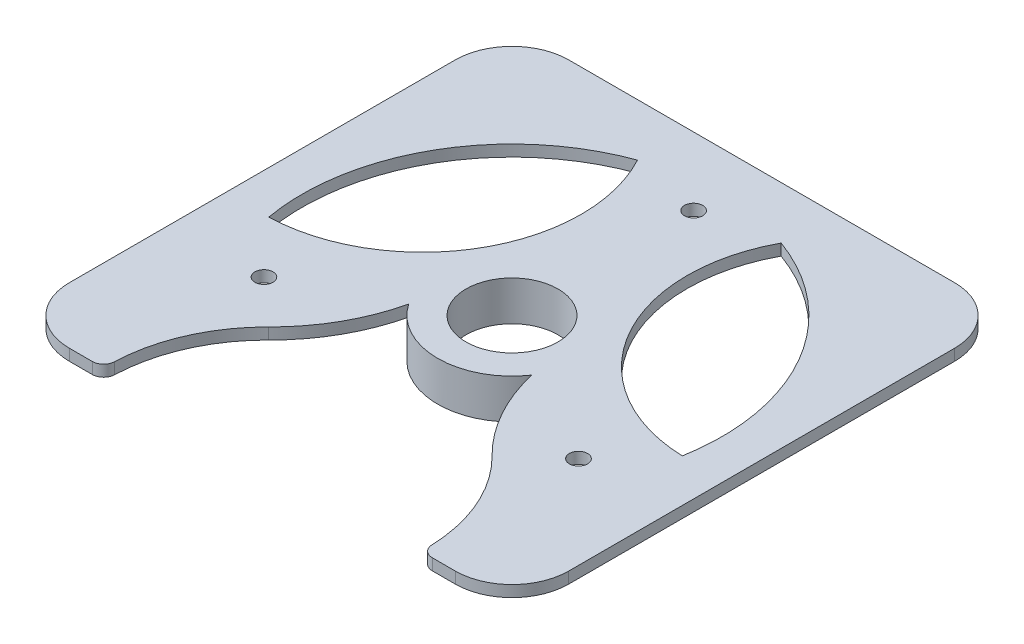
SolidWorks part; units mm, degrees
ref_plane "Front Plane" through (0, 0, 0) normal (0, 0, 1) x (1, 0, 0)
ref_plane "Top Plane" through (0, 0, 0) normal (0, 1, 0) x (1, 0, 0)
ref_plane "Right Plane" through (0, 0, 0) normal (1, 0, 0) x (0, 0, -1)
sketch "Sketch1" plane through (0, 0, 0) normal (0, 1, 0) x (1, 0, 0)
  line L0 (-44, 0) -> (-44, -44) construction
  line L1 (-44, -44) -> (44, -44) construction
  line L2 (44, -44) -> (44, 0) construction
  line L4 (-44, -44) -> (44, -44)
  line L5 (-44, -44) -> (-44, 44)
  line L6 (-44, 44) -> (44, 44)
  line L7 (44, -44) -> (44, 44)
  arc A0 (44, 0) -> (-44, 0) centre (0, 0) ccw construction
  dimension "D1" = 88
extrude "Boss-Extrude1" add sketch "Sketch1" along normal blind 2
fillet "Fillet1" radius 10 4 edges at (44, 1, 44) (-44, 1, 44) (44, 1, -44) (-44, 1, -44)
sketch "Sketch3" plane through (0, 2, 0) normal (0, 1, 0) x (1, 0, 0)
  circle A0 centre (0, 0) radius 37
  dimension "D1" = 74
extrude "Cut-Extrude2" cut sketch "Sketch3" against normal through all
sketch "Sketch5" plane through (0, 0, 0) normal (0, 1, 0) x (1, 0, 0)
  circle A0 centre (0, 0) radius 40.5
  circle A1 centre (0, 0) radius 10
  dimension "D1" = 20
extrude "Boss-Extrude2" add sketch "Sketch5" along normal up to surface (2 mm away) up to face at (0, 2, 37)
sketch "Sketch6" plane through (0, 2, 0) normal (0, 1, 0) x (1, 0, 0)
  line L0 (-12.6547, 34.7686) -> (0, 0) construction
  line L1 (0, 0) -> (12.6547, 34.7686) construction
  line L2 (0, -1000) -> (0, 49000) construction
  line L3 (-12.6547, 34.7686) -> (-9.9186, 27.2511)
  line L4 (9.9186, 27.2511) -> (12.6547, 34.7686)
  line L5 (36.4379, -6.425) -> (28.5594, -5.0358)
  line L6 (18.6408, -22.2153) -> (23.7831, -28.3436)
  line L7 (-23.7831, -28.3436) -> (-18.6408, -22.2153)
  line L8 (-28.5594, -5.0358) -> (-36.4379, -6.425)
  arc A0 (28.5594, -5.0358) -> (18.6408, -22.2153) centre (0, 0) cw
  arc A1 (-12.6547, 34.7686) -> (12.6547, 34.7686) centre (0, 0) cw
  arc A2 (-9.9186, 27.2511) -> (9.9186, 27.2511) centre (0, 0) cw
  circle A3 centre (0, 0) radius 37 construction
  arc A4 (36.4379, -6.425) -> (23.7831, -28.3436) centre (0, 0) cw
  arc A5 (-18.6408, -22.2153) -> (-28.5594, -5.0358) centre (0, 0) cw
  arc A6 (-23.7831, -28.3436) -> (-36.4379, -6.425) centre (0, 0) cw
  point P20 (0, 0)
  dimension "D3" = 8
  dimension "D4" = 74
  dimension "D1" = 20
  dimension "D2" = 20
  dimension "D5" = 3
sketch "Sketch16" plane through (0, 2, 0) normal (0, 1, 0) x (1, 0, 0)
  arc A0 (12.6547, 34.7686) -> (36.4379, -6.425) centre (37.307, 21.5392) ccw
  circle A1 centre (0, 0) radius 37 construction
  arc A2 (36.4379, -6.425) -> (12.6547, 34.7686) centre (0, 0) ccw
extrude "Cut-Extrude3" cut sketch "Sketch16" against normal through all
pattern_circular "CirPattern1" count 3 over 360 about axis through (0, 116.5513, 0) along (0, -1, 0) of "Cut-Extrude3" reverse direction yes
sketch "Sketch17" plane through (0, 2, 0) normal (0, 1, 0) x (1, 0, 0)
  circle A0 centre (0, -43.0784) radius 27.9777
  arc A1 (23.7831, -28.3436) -> (-23.7831, -28.3436) centre (0, -43.0784) ccw construction
extrude "Cut-Extrude4" cut sketch "Sketch17" against normal through all
sketch "Sketch18" plane through (0, 2, 0) normal (0, 1, 0) x (1, 0, 0)
  arc A0 (-10, 0) -> (-19.678, -23.1905) centre (-42.6237, 0) cw
  arc A1 (10, 0) -> (19.678, -23.1905) centre (42.6237, 0) ccw
  arc A2 (27.9625, -44) -> (-27.9625, -44) centre (0, -43.0784) ccw construction
  circle A3 centre (0, 0) radius 10 construction
  arc A4 (-10, 0) -> (10, 0) centre (0, 0) ccw
  arc A5 (19.678, -23.1905) -> (-19.678, -23.1905) centre (0, -43.0784) ccw
extrude "Cut-Extrude5" cut sketch "Sketch18" against normal through all
fillet "Fillet2" radius 2 2 edges at (27.9625, 1, 44) (-27.9625, 1, 44)
sketch "Sketch19" plane through (0, 0, 0) normal (0, -1, 0) x (1, 0, 0)
  circle A0 centre (0, 0) radius 8.1
  circle A1 centre (0, 0) radius 13.1
  dimension "D1" = 16.2
  dimension "D2" = 5
extrude "Boss-Extrude3" add sketch "Sketch19" along normal blind 5 and the other way up to surface (2 mm away) other way up to face at (-22.5603, 2, -13.0252)
sketch "Sketch20" plane through (0, 0, 0) normal (0, -1, 0) x (1, 0, 0)
  line L1 (0, -1000) -> (0, 49000) construction
  line L2 (0, -32) -> (0, 0) construction
  circle A0 centre (0, -32) radius 1.6
  dimension "D1" = 3.2
  dimension "D2" = 32
  dimension "D3" = 0
extrude "Cut-Extrude6" cut sketch "Sketch20" against normal through all
pattern_circular "CirPattern2" count 3 over 360 about axis through (0, 0, 0) along (0, 1, 0) of "Cut-Extrude6" reverse direction yes
